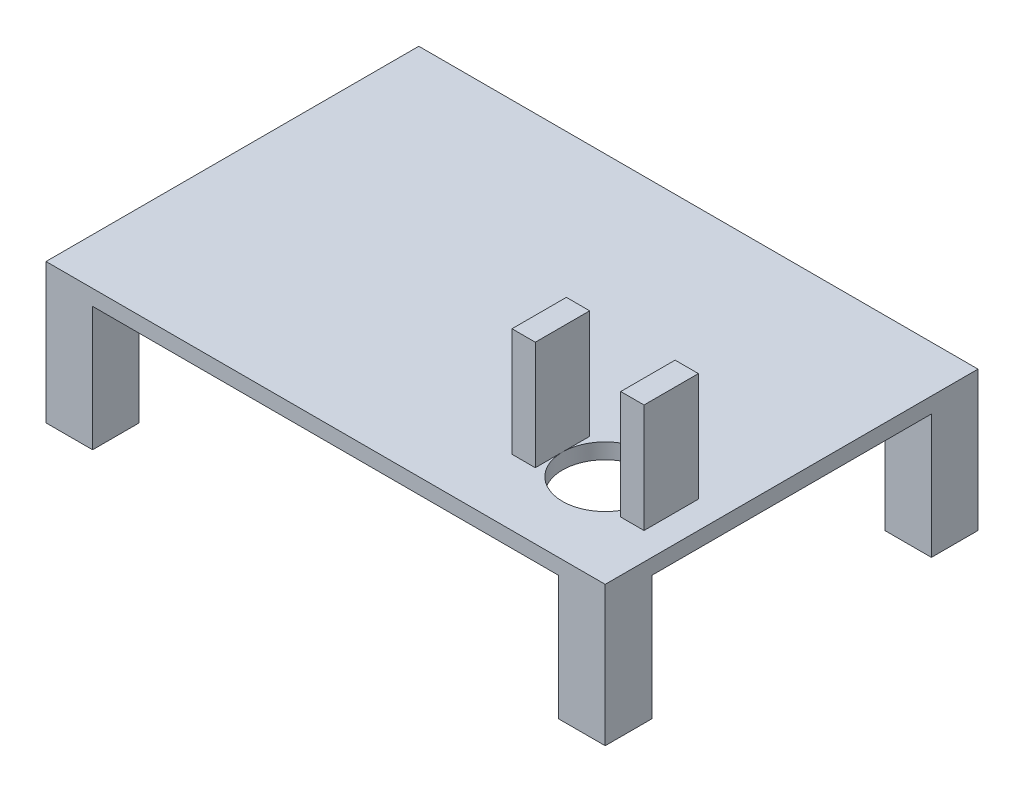
SolidWorks part; units mm, degrees
material "Cedar"
ref_plane "Front" through (0, 0, 0) normal (0, 0, 1) x (1, 0, 0)
ref_plane "Top" through (0, 0, 0) normal (0, 1, 0) x (1, 0, 0)
ref_plane "Right" through (0, 0, 0) normal (1, 0, 0) x (0, 0, -1)
sketch "Sketch1" plane through (0, 0, 0) normal (0, 1, 0) x (1, 0, 0)
  line L1 (0, 0) -> (914.4, 0)
  line L2 (0, 0) -> (0, 609.6)
  line L3 (0, 609.6) -> (914.4, 609.6)
  line L4 (914.4, 0) -> (914.4, 609.6)
  line L5 (654.05, 196.85) -> (692.15, 196.85)
  line L6 (654.05, 196.85) -> (654.05, 107.95)
  line L7 (654.05, 107.95) -> (692.15, 107.95)
  line L8 (692.15, 196.85) -> (692.15, 107.95)
  line L9 (869.95, 196.85) -> (831.85, 196.85)
  line L10 (869.95, 196.85) -> (869.95, 107.95)
  line L11 (869.95, 107.95) -> (831.85, 107.95)
  line L12 (831.85, 196.85) -> (831.85, 107.95)
  circle A0 centre (762, 152.4) radius 69.85
  point P15 (692.15, 152.4)
  point P16 (831.85, 152.4)
  dimension "D3" = 139.7
  dimension "D1" = 609.6
  dimension "D2" = 914.4
  dimension "D4" = 38.1
  dimension "D5" = 88.9
  dimension "D6" = 38.1
  dimension "D7" = 88.9
  dimension "D8" = 152.4
  dimension "D9" = 152.4
extrude "Boss-Extrude2" add sketch "Sketch1" along normal blind 25.4 contours L1 L4 L3 L2 A0 L12 L9 L10 L11 L8 L7 L6 L5 | L8 L5 L6 L7 | A0 | L9 L12 L11 L10 region at (444.6154, 0, -311.0923) region at (850.9, 0, -152.4) region at (762, 0, -152.4) region at (673.1, 0, -152.4)
extrude "Cut-Extrude2" cut sketch "Sketch1<3>" along normal through all contours A0
sketch "Sketch1<3>" plane through (0, 0, 0) normal (0, 1, 0) x (1, 0, 0) same geometry as "Sketch1"
extrude "Boss-Extrude3" add sketch "Sketch1<4>" along normal blind 203.2 contours L7 L8 L5 L6 | L11 L12 L9 L10
sketch "Sketch1<4>" plane through (0, 0, 0) normal (0, 1, 0) x (1, 0, 0) same geometry as "Sketch1"
sketch "Sketch3" plane through (0, 0, 0) normal (0, -1, 0) x (1, 0, 0)
  line L0 (76.2, -533.4) -> (76.2, -609.6)
  line L1 (0, 0) -> (76.2, 0)
  line L2 (0, 0) -> (0, -76.2)
  line L3 (0, -76.2) -> (76.2, -76.2)
  line L4 (76.2, 0) -> (76.2, -76.2)
  line L5 (0, -609.6) -> (76.2, -609.6)
  line L6 (0, -533.4) -> (0, -609.6)
  line L7 (0, -533.4) -> (76.2, -533.4)
  line L8 (914.4, -533.4) -> (914.4, -609.6)
  line L9 (838.2, -609.6) -> (914.4, -609.6)
  line L10 (838.2, -533.4) -> (838.2, -609.6)
  line L11 (838.2, -533.4) -> (914.4, -533.4)
  line L12 (914.4, 0) -> (914.4, -76.2)
  line L13 (838.2, -76.2) -> (914.4, -76.2)
  line L14 (838.2, 0) -> (838.2, -76.2)
  line L15 (838.2, 0) -> (914.4, 0)
  dimension "D1" = 76.2
  dimension "D2" = 2
  dimension "3in" = 76.2
  dimension "D3" = 2
extrude "Boss-Extrude4" add sketch "Sketch3" along normal blind 203.2
